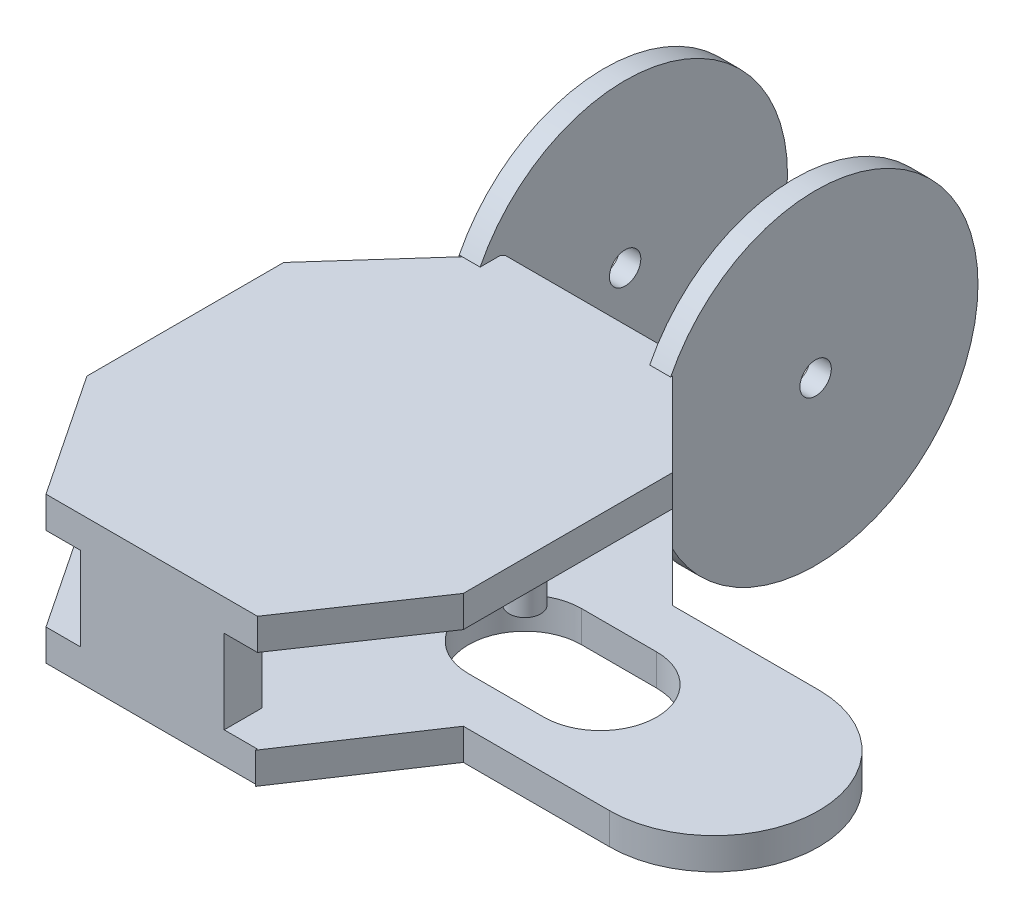
SolidWorks part; units mm, degrees
ref_plane "Front Plane" through (0, 0, 0) normal (0, 0, 1) x (1, 0, 0)
ref_plane "Top Plane" through (0, 0, 0) normal (0, 1, 0) x (1, 0, 0)
ref_plane "Right Plane" through (0, 0, 0) normal (1, 0, 0) x (0, 0, -1)
sketch "Sketch1" plane through (0, 0, 0) normal (0, 1, 0) x (1, 0, 0)
  line L0 (0, 33.8197) -> (10, 45)
  line L1 (0, 0) -> (60, 0)
  line L2 (0, 0) -> (0, 45)
  line L3 (0, 45) -> (60, 45)
  line L4 (60, 0) -> (60, 45)
  line L5 (0, 15) -> (10, 0)
  line L6 (26, 45) -> (36, 35)
  line L7 (26, 0) -> (36, 15)
  line L8 (36, 15) -> (60, 15)
  line L9 (36, 35) -> (60, 35)
  line L10 (60, 25) -> (0, 25) construction
  line L12 (44.5, 19.6) -> (26.5, 19.6)
  line L13 (44.5, 19.6) -> (44.5, 30.4)
  line L14 (44.5, 30.4) -> (26.5, 30.4)
  line L15 (26.5, 19.6) -> (26.5, 30.4)
  circle A0 centre (5, 25) radius 1.5
  circle A1 centre (13, 5) radius 1.5
  circle A2 centre (23, 5) radius 1.5
  dimension "D14" = 3
  dimension "D15" = 10
  dimension "D16" = 3
  dimension "D24" = 3
  dimension "D25" = 3
  dimension "D17" = 3
  dimension "D1" = 45
  dimension "D2" = 60
  dimension "D3" = 15
  dimension "D4" = 10
  dimension "D5" = 10
  dimension "D6" = 15
  dimension "D7" = 16
  dimension "D8" = 16
  dimension "D9" = 10
  dimension "D10" = 10
  dimension "D11" = 10
  dimension "D12" = 20
  dimension "D13" = 10
  dimension "D18" = 5
  dimension "D19" = 5
  dimension "D20" = 4.6
  dimension "D21" = 4.6
  dimension "D22" = 15.5
  dimension "D23" = 18
extrude "Boss-Extrude1" add sketch "Sketch1" along normal blind 3 contours L4 L10 L13 L12 L15 A0 L2 L5 L1 L7 L8 | L10 L4 L9 L6 L3 L0 L2 A0 L15 L14 L13 region at (25.4751, 0, -33.485) region at (24.3362, 0, -14.8271)
fillet "Fillet5" 2 edges at (60, 1.5, -35) (60, 1.5, -15) type full round first side face at (48, 1.5, -35) second side face at (48, 1.5, -15) middle face at (60, 1.5, -25)
fillet "Fillet2" 2 edges at (26.5, 1.5, -19.6) (26.5, 1.5, -30.4) type full round first side face at (35.5, 1.5, -19.6) second side face at (35.5, 1.5, -30.4) middle face at (26.5, 1.5, -25)
fillet "Fillet4" 2 edges at (44.5, 1.5, -30.4) (44.5, 1.5, -19.6) type full round first side face at (38.2, 1.5, -30.4) second side face at (38.2, 1.5, -19.6) middle face at (44.5, 1.5, -25)
sketch "Sketch2" plane through (0, 3, 0) normal (0, 1, 0) x (1, 0, 0)
  line L0 (0, 15) -> (10, 0) construction
  line L1 (7.8248, 3.2628) -> (28.0475, 3.2628)
  line L2 (7.8248, 3.2628) -> (7.8248, -1.1995)
  line L3 (7.8248, -1.1995) -> (28.0475, -1.1995)
  line L4 (28.0475, 3.2628) -> (28.0475, -1.1995)
extrude "Cut-Extrude1" cut sketch "Sketch2" against normal blind 6
sketch "Sketch3" plane through (0, 3, 0) normal (0, 1, 0) x (1, 0, 0)
  line L0 (10, 45) -> (0, 33.8197)
  line L1 (0, 33.8197) -> (0, 15)
  line L2 (0, 15) -> (7.8248, 3.2628)
  line L3 (7.8248, 3.2628) -> (28.0475, 3.2628)
  line L4 (28.0475, 3.2628) -> (36, 15)
  line L5 (36, 15) -> (36, 35)
  line L6 (36, 35) -> (26, 45)
  line L7 (26, 45) -> (10, 45)
extrude "Boss-Extrude2" add sketch "Sketch3" along normal blind 3 from offset 8 separate body
sketch "Sketch4" plane through (0, 3, 0) normal (0, 1, 0) x (1, 0, 0)
  line L1 (26, 45) -> (9.7798, 45)
  line L2 (26, 45) -> (26, 42.9505)
  line L3 (26, 42.9505) -> (9.7798, 42.9505)
  line L4 (9.7798, 45) -> (9.7798, 42.9505)
  line L5 (11.1389, 3.2628) -> (24.8678, 3.2628)
  line L6 (11.1389, 3.2628) -> (11.1389, 6.8968)
  line L7 (11.1389, 6.8968) -> (24.8678, 6.8968)
  line L8 (24.8678, 3.2628) -> (24.8678, 6.8968)
extrude "Boss-Extrude3" add sketch "Sketch4" along normal blind 8
sketch "Sketch5" plane through (0, 14, 0) normal (0, 1, 0) x (1, 0, 0)
  circle A0 centre (5, 25) radius 1.5
extrude "Boss-Extrude4" add sketch "Sketch5" against normal blind 8
sketch "Sketch6" plane through (0, 14, 0) normal (0, 1, 0) x (1, 0, 0)
  circle A0 centre (31.9, 25) radius 1.5
extrude "Boss-Extrude5" add sketch "Sketch6" against normal blind 8
sketch "Sketch7" plane through (9.7798, 0, 0) normal (-1, 0, 0) x (0, 0, 1)
  line L0 (-33.8197, 0) -> (-45, 0) construction
  line L1 (-45, 14) -> (-33.8197, 14) construction
  line L2 (-42.8037, 0.0517) -> (-42.8297, 0)
  line L3 (-42.8297, 0) -> (-42.8297, 14)
  circle A0 centre (-56.6952, 7) radius 15.5324
  line M2 (-45, 3) -> (-44.7538, 3)
  line M3 (-44.7538, 3) -> (-42.9505, 3)
  line M4 (-42.9505, 3) -> (-42.9505, 11)
  line M5 (-42.9505, 11) -> (-44.7538, 11)
  line M6 (-44.7538, 11) -> (-45, 11)
  line M7 (-45, 11) -> (-45, 3)
  dimension "D1" = 7
  dimension "D2" = 7
extrude "Boss-Extrude9" add sketch "Sketch7" along normal blind 2 contours L3 A0 M2 M7 M6 M5 M4 M3 | M7 M2 M3 M4 M5 M6 region at (9.7798, 7, -57.2977) region at (9.7798, 7, -43.9752)
sketch "Sketch10" plane through (26, 0, 0) normal (1, 0, 0) x (0, 0, -1)
  line L0 (42.8297, 14) -> (42.8297, 0)
  circle A1 centre (56.6952, 7) radius 15.5324
  line M1 (42.9505, 3) -> (45, 3)
  line M2 (45, 3) -> (45, 11)
  line M3 (45, 11) -> (42.9505, 11)
  line M4 (42.9505, 11) -> (42.9505, 3)
extrude "Boss-Extrude10" add sketch "Sketch10" along normal blind 2 contours L0 A1 M1 M4 M3 M2 | M4 M1 M2 M3 region at (26, 7, -57.2977) region at (26, 7, -43.9752)
sketch "Sketch11" plane through (7.7798, 0, 0) normal (-1, 0, 0) x (0, 0, 1)
  circle A0 centre (-56.6952, 7) radius 1.5
extrude "Cut-Extrude2" cut sketch "Sketch11" against normal blind 21
